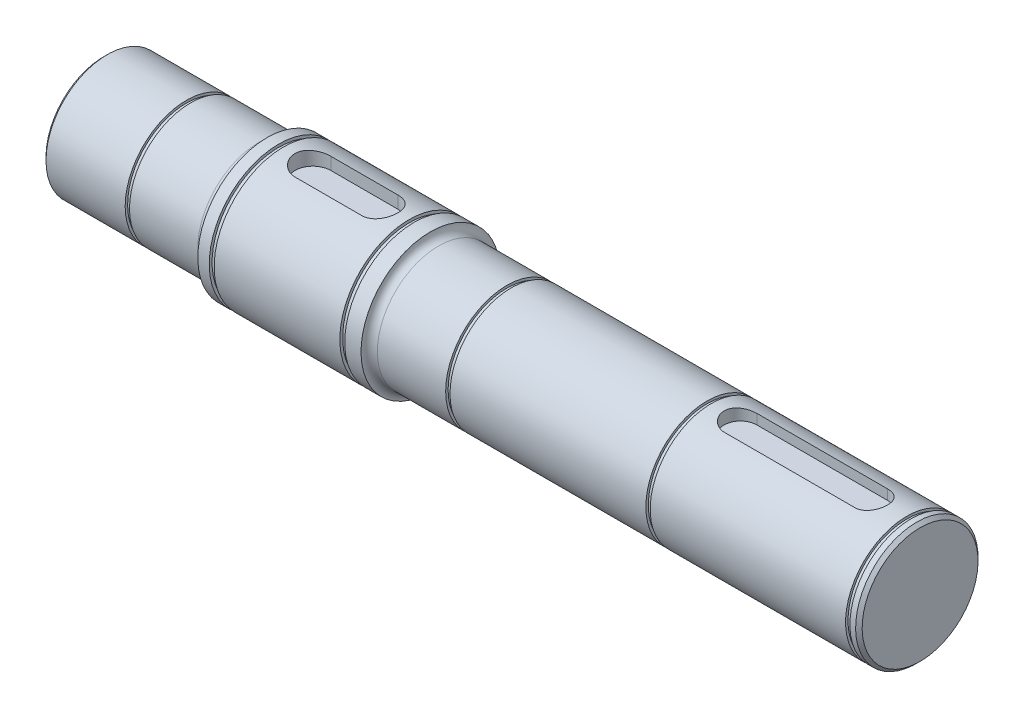
SolidWorks part; units mm, degrees
ref_plane "Front" through (0, 0, 0) normal (0, 0, 1) x (1, 0, 0)
ref_plane "Top" through (0, 0, 0) normal (0, 1, 0) x (1, 0, 0)
ref_plane "Right" through (0, 0, 0) normal (1, 0, 0) x (0, 0, -1)
sketch "Esquisse1" plane through (0, 0, 0) normal (0, 0, 1) x (1, 0, 0)
  line L0 (0, 0) -> (0, 37.5)
  line L1 (0, 37.5) -> (95, 37.5)
  line L3 (100, 42.5) -> (200, 42.5)
  line L5 (205, 37.5) -> (500, 37.5)
  line L6 (500, 37.5) -> (500, 0)
  line L7 (500, 0) -> (0, 0)
  arc A0 (100, 42.5) -> (95, 37.5) centre (95, 42.5) cw
  arc A1 (200, 42.5) -> (205, 37.5) centre (205, 42.5) ccw
  dimension "D4" = 5
  dimension "D6" = 5
  dimension "D1" = 37.5
  dimension "D2" = 100
  dimension "D3" = 500
  dimension "D5" = 42.5
  dimension "D7" = 100
revolve "Révolution1" add sketch "Esquisse1" angle 360 about L7
ref_plane "Plan1" through (110, 0, 0) normal (1, 0, 0) x (0, 0, -1)
ref_plane "Plan2" through (190, 0, 0) normal (1, 0, 0) x (0, 0, -1)
sketch "Esquisse2" plane through (110, 0, 0) normal (1, 0, 0) x (0, 0, -1)
  circle A0 centre (0, 0) radius 42.5 construction
  circle A2 centre (0, 0) radius 42.5
  circle A3 centre (0, 0) radius 40.75
  dimension "D1" = 1.75
extrude "Enlèv. mat.-Extru.1" cut sketch "Esquisse2" against normal blind 3
sketch "Esquisse3" plane through (190, 0, 0) normal (1, 0, 0) x (0, 0, -1)
  circle A0 centre (0, 0) radius 42.5 construction
  circle A1 centre (0, 0) radius 42.5
  circle A2 centre (0, 0) radius 40.75
  dimension "D1" = 1.75
extrude "Enlèv. mat.-Extru.2" cut sketch "Esquisse3" against normal blind 3
ref_plane "Plan3" through (0, 42.5, 0) normal (0, 1, 0) x (1, 0, 0)
sketch "Esquisse4" plane through (0, 42.5, 0) normal (0, 1, 0) x (1, 0, 0)
  line L0 (148.5, 42.5) -> (148.5, 0) construction
  line L1 (187, 42.5) -> (110, 42.5) construction
  line L2 (128, 0) -> (169, 0) construction
  line L3 (128, 11) -> (169, 11)
  line L4 (128, -11) -> (169, -11)
  arc A0 (128, 11) -> (128, -11) centre (128, 0) ccw
  arc A1 (169, -11) -> (169, 11) centre (169, 0) ccw
  point P6 (148.5, 0)
  dimension "D2" = 11
  dimension "D1" = 41
extrude "Enlèv. mat.-Extru.3" cut sketch "Esquisse4" against normal blind 9
ref_plane "Plan4" through (0, 37.5, 0) normal (0, 1, 0) x (1, 0, 0)
sketch "Esquisse5" plane through (0, 37.5, 0) normal (0, 1, 0) x (1, 0, 0)
  line L0 (500, 0) -> (430, 0) construction
  line L1 (500, -37.5) -> (500, 37.5) construction
  line L2 (470, 0) -> (390, 0) construction
  line L3 (470, -10) -> (390, -10)
  line L4 (470, 10) -> (390, 10)
  arc A0 (470, -10) -> (470, 10) centre (470, 0) ccw
  arc A1 (390, 10) -> (390, -10) centre (390, 0) ccw
  point P7 (430, 0)
  dimension "D2" = 10
  dimension "D1" = 70
  dimension "D3" = 80
extrude "Enlèv. mat.-Extru.4" cut sketch "Esquisse5" against normal blind 7.5
chamfer "Chanfrein1" distance 2 angle 45 2 edges at (500, 37.5, 0) (0, 37.5, 0)
ref_plane "Plan5" through (494.5, 0, 0) normal (1, 0, 0) x (0, 0, -1)
sketch "Esquisse6" plane through (494.5, 0, 0) normal (1, 0, 0) x (0, 0, -1)
  circle A0 centre (0, 0) radius 37.5 construction
  circle A1 centre (0, 0) radius 37.5
  circle A2 centre (0, 0) radius 36
  dimension "D1" = 1.5
extrude "Enlèv. mat.-Extru.5" cut sketch "Esquisse6" against normal blind 2.65
ref_plane "Plan6" through (50.5, 0, 0) normal (-1, 0, 0) x (0, 0, 1)
sketch "Esquisse7" plane through (50.5, 0, 0) normal (-1, 0, 0) x (0, 0, 1)
  circle A0 centre (0, 0) radius 37.5 construction
  circle A1 centre (0, 0) radius 37.5
  circle A2 centre (0, 0) radius 36
  dimension "D1" = 1.5
extrude "Enlèv. mat.-Extru.6" cut sketch "Esquisse7" against normal blind 2.65
ref_plane "Plan8" through (249.5, 0, 0) normal (-1, 0, 0) x (0, 0, 1)
sketch "Esquisse8" plane through (249.5, 0, 0) normal (-1, 0, 0) x (0, 0, 1)
  circle A0 centre (0, 0) radius 37.5 construction
  circle A1 centre (0, 0) radius 37.5
  circle A2 centre (0, 0) radius 36
  dimension "D1" = 1.5
extrude "Enlèv. mat.-Extru.7" cut sketch "Esquisse8" along normal blind 2.65
ref_plane "Plan9" through (369.5, 0, 0) normal (1, 0, 0) x (0, 0, -1)
sketch "Esquisse10" plane through (369.5, 0, 0) normal (1, 0, 0) x (0, 0, -1)
  circle A0 centre (0, 0) radius 37.5 construction
  circle A1 centre (0, 0) radius 37.5
  circle A2 centre (0, 0) radius 36
  dimension "D1" = 1.5
extrude "Enlèv. mat.-Extru.11" cut sketch "Esquisse10" along normal blind 2.65
